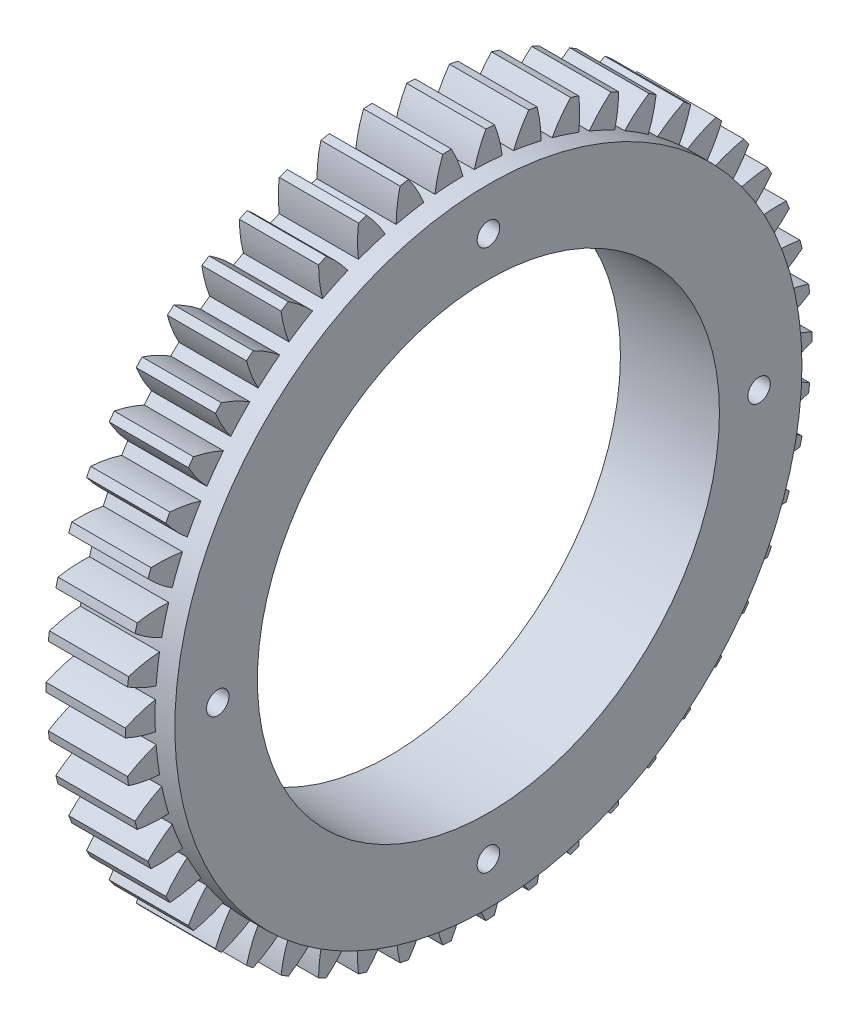
SolidWorks part; units mm, degrees
ref_plane "Plane1" through (0, 0, 0) normal (0, 0, 1) x (1, 0, 0)
ref_plane "Plane2" through (0, 0, 0) normal (0, 1, 0) x (1, 0, 0)
ref_plane "Plane3" through (0, 0, 0) normal (1, 0, 0) x (0, 0, -1)
sketch "HoldingSke" plane through (0, 0, 0) normal (0, 1, 0) x (1, 0, 0)
  line L0 (0, 0) -> (0.3214, -0.383)
  line L1 (-15, 0) -> (100, 0) construction
  line L2 (0, 0) -> (-2.1039, 2.3779)
  line L3 (0, 0) -> (-11.863, 4.5341)
  line L4 (0, 0) -> (5.5511, 6.6156)
  line L5 (0, 0) -> (-46.8476, -17.4728)
  line L6 (0, 0) -> (-9.9476, -6.7116)
  line L7 (-2.1039, 2.3779) -> (8.6586, 51.206)
  line L8 (-76.2, 54.61) -> (-71.3, 54.61)
  line L9 (-71.009, 38.7566) -> (-53.1078, 45.2721)
  line L10 (-76.2, 71.12) -> (104.1128, 71.12)
  line L11 (0, 0) -> (-12, 0)
  line L12 (-76.2, 101.6) -> (-76.133, 101.6)
  line L13 (24.9733, 27.94) -> (52.9518, 28.4284)
  line L14 (24.9733, 27.94) -> (24.9743, 27.94)
  line L15 (24.9733, 27.94) -> (100.4006, 29.5858)
  line L16 (-63.627, -2) -> (-12.827, -2)
  circle A0 centre (0, 0) radius 35
  circle A1 centre (0, 0) radius 37.5
  circle A2 centre (0, 0) radius 37.5
  circle A3 centre (0, 0) radius 35
  dimension "Num_teeth" = 50
  dimension "Pitch_radius" = 180.3128
  dimension "Width" = 12
  dimension "Thickness" = 12
sketch "BasProSke" plane through (0, 0, 0) normal (0, 1, 0) x (1, 0, 0)
  line L0 (-10, 0) -> (60, 0) construction
  line L1 (0, 0) -> (0, 52)
  line L2 (0, 0) -> (12, 0)
  line L3 (12, 0) -> (12, 52)
  line L4 (12, 52) -> (0, 52)
  dimension "Thickness" = 12
  dimension "Diameter" = 104
revolve "Base-Revolve" add sketch "BasProSke" angle 360 about L0
sketch "TooCutSke" plane through (0, 0, 0) normal (1, 0, 0) x (0, 0, -1)
  line L1 (0, 0) -> (0, 107) construction
  line L2 (0, 0) -> (-1.6878, 49.9715) construction
  line L3 (0, 0) -> (-6.2764, 99.7605) construction
  line L4 (-1.6878, 49.9715) -> (-3.1382, 49.8803) construction
  arc A0 (0.8606, 47.4912) -> (-0.8606, 47.4912) centre (0, 0) ccw
  arc A1 (2.629, 51.9589) -> (-2.629, 51.9589) centre (0, 0) ccw
  circle A2 centre (0, 0) radius 50 construction
  circle A3 centre (0, 0) radius 46.9846 construction
  arc A4 (-0.8606, 47.4912) -> (-2.629, 51.9589) centre (-20.2064, 42.4176) ccw
  arc A5 (2.629, 51.9589) -> (0.8606, 47.4912) centre (20.2064, 42.4176) ccw
extrude "ToothCut" cut sketch "TooCutSke" along normal through all
fillet "Breaks" [suppressed] radius 0.04 tangent propagation no
fillet "RootFillets" [suppressed] radius 0.501
pattern_circular "TeethCuts" count 50 every 7.2 about axis through (-10, 0, 0) along (1, 0, 0) of "ToothCut"
sketch "HubNeaOneSke" plane through (0, 0, 0) normal (-1, 0, 0) x (0, 0, 1)
  circle A0 centre (0, 0) radius 37.5
  dimension "Diameter" = 75
extrude "HubNearOne" [suppressed] add sketch "HubNeaOneSke" along normal blind 38.0002
sketch "HubNeaBotSke" plane through (0, 0, 0) normal (-1, 0, 0) x (0, 0, 1)
  circle A0 centre (0, 0) radius 37.5
  dimension "Diameter" = 75
extrude "HubNearBoth" [suppressed] add sketch "HubNeaBotSke" along normal blind 19.0001
ref_plane "FarPln" through (12, 0, 0) normal (1, 0, 0) x (0, 0, -1)
sketch "HubFarSke" plane through (12, 0, 0) normal (1, 0, 0) x (0, 0, -1)
  circle A0 centre (0, 0) radius 37.5
  dimension "Diameter" = 75
extrude "HubFar" [suppressed] add sketch "HubFarSke" along normal blind 19.0001
sketch "BorSke" plane through (0, 0, 0) normal (1, 0, 0) x (0, 0, -1)
  circle A0 centre (0, 0) radius 35
  dimension "Diameter" = 70
extrude "Bore" cut sketch "BorSke" along normal mid plane 100.0003
sketch "KeySke" plane through (0, 0, 0) normal (1, 0, 0) x (0, 0, -1)
  line L0 (-10, 0) -> (-10, 39.9)
  line L1 (-10, 39.9) -> (10, 39.9)
  line L2 (10, 39.9) -> (10, 0)
  line L3 (0, 0) -> (0, 34) construction
  line L4 (-10, 0) -> (10, 0)
  dimension "Width" = 20
extrude "Keyway" [suppressed] cut sketch "KeySke" along normal mid plane 100.0003
pattern_circular "Keyway2" [suppressed] count 2 every 90 about axis through (-10, 0, 0) along (1, 0, 0)
sketch "Schizzo3" plane through (12, 0, 0) normal (1, 0, 0) x (0, 0, -1)
  circle A0 centre (0, 0) radius 47.499
  circle A1 centre (0, 0) radius 35
extrude "Estrusione-Estrusione1" add sketch "Schizzo3" along normal blind 3
hole_wizard "Foro per Vite M3-1" positions "Schizzo1" profile "Schizzo2" hole size "M3" standard "ISO"
sketch "Schizzo1" plane through (15, 0, 0) normal (1, 0, 0) x (0, 0, -1)
  circle A0 centre (0, 0) radius 41 construction
  point P0 (0, -41)
  point P2 (0, 41)
  point P4 (-41, 0)
  point P6 (41, 0)
  dimension "D1" = 82
sketch "Schizzo2" plane through (15, -41, 0) normal (0, 1, 0) x (0, 0, -1)
  line L0 (0, 0) -> (0, 189.0215)
  line L1 (0, 189.0215) -> (1.7, 188)
  line L2 (1.7, 188) -> (1.7, 0)
  line L5 (1.7, 0) -> (0, 0)
  line L10 (0, 189.0215) -> (-1.7, 188) construction
  line L11 (0, -6.35) -> (0, 107.95) construction
  dimension "Hole Dia." = 3.4
  dimension "Hole Depth" = 188
  dimension "Drill Angle" = 118
equation "' \"Module@HoldingSke\" = 6.35"
equation "' \"Num_teeth@HoldingSke\" = 12"
equation "' \"Ap@HoldingSke\" =  20"
equation "' \"Ap@HoldingSke\" = 20"
equation "' \"Width@HoldingSke\" = 0.5 * 25.4"
equation "' \"Hub_dia@HoldingSke\"= 1 * 25.4"
equation "' \"Hub_dia@HoldingSke\" = 1 * 25.4"
equation "' \"Overall_len@HoldingSke\" = 1.0 * 25.4"
equation "' \"Bore@HoldingSke\" = 0.75 * 25.4"
equation "' \"T_dim@HoldingSke\" = 0.1 * 25.4"
equation "' \"Width@KeySke\" = 0.25 * 25.4"
equation "' \"Show_teeth@HoldingSke\" = 13"
equation "' \"Backlash@HoldingSke\" = 0.009 * 25.4"
equation "' \"Addendum_fac@HoldingSke\" = 1.0"
equation "' \"Dedendum_fac@HoldingSke\" = 1.25"
equation "' \"Dedendum_add@HoldingSke\" = 0.00005 * 25.4"
equation "' \"Clearance_fac@HoldingSke\" = 0.25"
equation "\"Pitch@HoldingSke\" = 1 / \"Module@HoldingSke\""
equation "\"Overcut_dia@TooCutSke\" = (\"Num_teeth@HoldingSke\" + 2 * \"Addendum_fac@HoldingSke\") / \"Pitch@HoldingSke\" + 0.002 * 25.4"
equation "\"Pitch_dia@TooCutSke\" = \"Num_teeth@HoldingSke\" / \"Pitch@HoldingSke\""
equation "\"Base_dia@TooCutSke\" = \"Num_teeth@HoldingSke\" / \"Pitch@HoldingSke\" * cos((\"Ap@HoldingSke\"  * 3.14159265 / 180))"
equation "\"Root_dia@TooCutSke\" = (\"Num_teeth@HoldingSke\" + 2) / \"Pitch@HoldingSke\" - 2 * (\"Addendum_fac@HoldingSke\" + \"Dedendum_fac@HoldingSke\") / \"Pitch@HoldingSke\" - \"Dedendum_add@HoldingSke\" * 2"
equation "\"Half_ang@TooCutSke\" = 180 / \"Num_teeth@HoldingSke\""
equation "\"Half_CT@TooCutSke\" = \"Num_teeth@HoldingSke\" / \"Pitch@HoldingSke\" * sin((3.14159265 / 2 / \"Num_teeth@HoldingSke\")) / 2 - 7 * \"Backlash@HoldingSke\" / 4"
equation "\"Flank_rad@TooCutSke\" = \"Num_teeth@HoldingSke\" / \"Pitch@HoldingSke\" / 5"
equation "\"Radius@RootFillets\" = \"Clearance_fac@HoldingSke\" / \"Pitch@HoldingSke\" + \"Dedendum_add@HoldingSke\""
equation "\"Break_rad@Breaks\" = 0.02 / \"Pitch@HoldingSke\""
equation "\"Thickness@HoldingSke\" = \"Width@HoldingSke\""
equation "\"OAL@HoldingSke\" = ((sgn( \"OAL@HoldingSke\" - \"Overall_len@HoldingSke\" )+1)*( \"OAL@HoldingSke\" - \"Overall_len@HoldingSke\" ))/2 + \"Overall_len@HoldingSke\" + 0.000002 * 25.4"
equation "\"MHD@HoldingSke\" = ((sgn( \"MHD@HoldingSke\" - \"Root_dia@TooCutSke\" )-1)*( \"MHD@HoldingSke\" - \"Root_dia@TooCutSke\" ))/-2+ \"Root_dia@TooCutSke\""
equation "\"MBD@HoldingSke\" = ((sgn( \"MBD@HoldingSke\" - \"Bore@HoldingSke\" )-1)*( \"MBD@HoldingSke\" - \"Bore@HoldingSke\" ))/-2+ \"Bore@HoldingSke\""
equation "\"Num_teeth@TeethCuts\" = ((sgn( \"Num_teeth@TeethCuts\" - 2.0)+1)*( \"Num_teeth@TeethCuts\" - 2.0))/2 +2.0"
equation "\"Angle@TeethCuts\" = 360.0 / \"Num_teeth@HoldingSke\""
equation "\"Diameter@BasProSke\" = (\"Num_teeth@HoldingSke\" + 2 * \"Addendum_fac@HoldingSke\") / \"Pitch@HoldingSke\""
equation "\"Thickness@BasProSke\"  = \"Thickness@HoldingSke\""
equation "' \"Fillet_rad@BasProSke\" =  \"Thickness@HoldingSke\" * 0.05"
equation "' \"Fillet_rad@BasProSke\" = \"Thickness@HoldingSke\" * 0.05"
equation "\"Diameter@HubNeaOneSke\" = \"MHD@HoldingSke\""
equation "\"Length@HubNearOne\" = \"OAL@HoldingSke\" - \"Thickness@BasProSke\""
equation "\"Diameter@HubNeaBotSke\" = \"MHD@HoldingSke\""
equation "\"Length@HubNearBoth\" = ( \"OAL@HoldingSke\" - \"Thickness@BasProSke\" ) / 2.0"
equation "\"Thickness@FarPln\" = \"Thickness@BasProSke\""
equation "\"Diameter@HubFarSke\" = \"MHD@HoldingSke\""
equation "\"Length@HubFar\" = ( \"OAL@HoldingSke\" - \"Thickness@BasProSke\" ) / 2.0"
equation "\"Diameter@BorSke\" = \"MBD@HoldingSke\""
equation "\"D1@Bore\" = \"OAL@HoldingSke\" * 2.0"
equation "\"D1@Keyway\" = \"OAL@HoldingSke\" * 2.0"
equation "\"Offset@KeySke\" = \"T_dim@HoldingSke\" + \"MBD@HoldingSke\" / 2.0"
